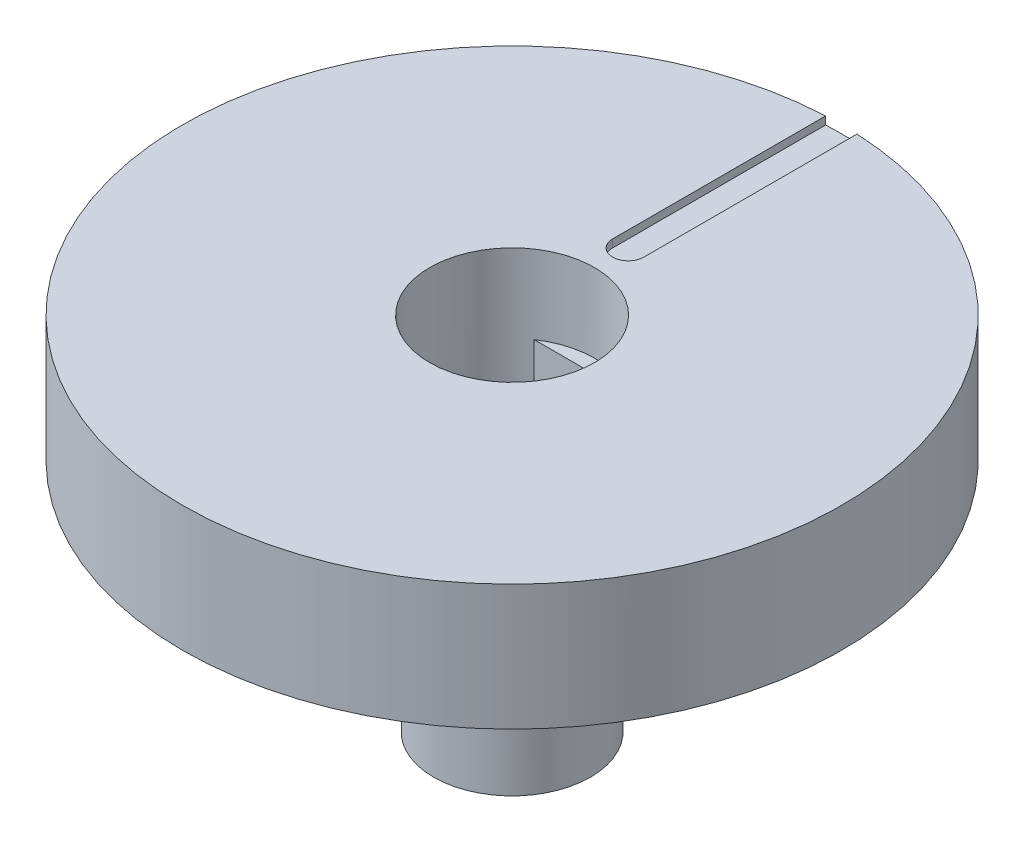
SolidWorks part; units mm, degrees
ref_plane "Front Plane" through (0, 0, 0) normal (0, 0, 1) x (1, 0, 0)
ref_plane "Top Plane" through (0, 0, 0) normal (0, 1, 0) x (1, 0, 0)
ref_plane "Right Plane" through (0, 0, 0) normal (1, 0, 0) x (0, 0, -1)
sketch "Sketch1" plane through (0, 0, 0) normal (0, 1, 0) x (1, 0, 0)
  circle A0 centre (0, 0) radius 8.6
  circle A1 centre (0, 0) radius 10.5
  dimension "D1" = 17.2
  dimension "D2" = 21
extrude "Boss-Extrude1" add sketch "Sketch1" against normal blind 3.5
ref_plane "Plane1" through (0, 0, 8.6) normal (0, 0, -1) x (-1, 0, 0)
sketch "Sketch2" plane through (0, 0, 8.6) normal (0, 0, -1) x (-1, 0, 0)
  line L0 (0.4, -2.9) -> (-0.4, -2.9)
  line L1 (0.4, -2.9) -> (0.4, -1)
  line L2 (0.4, -1) -> (1.4, 0)
  line L3 (10.5, 0) -> (-10.5, 0) construction
  line L4 (1.4, 0) -> (-1.4, 0)
  line L5 (-1.4, 0) -> (-0.4, -1)
  line L6 (-0.4, -1) -> (-0.4, -2.9)
  point P2 (0, -2.9)
  dimension "D1" = 2.9
  dimension "D2" = 135
  dimension "D3" = 135
  dimension "D4" = 0.8
  dimension "D5" = 1
extrude "Boss-Extrude2" add sketch "Sketch2" along normal blind 1.25
ref_plane "Plane2" through (0, 0, -8.6) normal (0, 0, 1) x (1, 0, 0)
extrude "Boss-Extrude3" add sketch "Sketch2<2>" against normal blind 1.25 from surface starting at plane "Plane2"
sketch "Sketch2<2>" plane through (0, 0, 8.6) normal (0, 0, -1) x (-1, 0, 0) same geometry as "Sketch2"
sketch "Sketch3" plane through (0, 0, 0) normal (0, 1, 0) x (1, 0, 0)
  circle A1 centre (0, 0) radius 10.5
  circle A2 centre (0, 0) radius 10.5
  dimension "D1" = 0
extrude "Boss-Extrude4" add sketch "Sketch3" along normal blind 0.5
sketch "Sketch5" plane through (0, 0, 0) normal (0, -1, 0) x (1, 0, 0)
  circle A1 centre (0, 0) radius 3.25
  dimension "D2" = 6.5
extrude "Boss-Extrude5" add sketch "Sketch5" along normal blind 6
fillet "Fillet2" radius 0.75 1 edges at (0, 0, 3.25)
sketch "Sketch4" plane through (0, 0.5, 0) normal (0, 1, 0) x (1, 0, 0)
  line L0 (-1.4697, 2.175) -> (1.4697, 2.175)
  line L1 (-3.1755, -2.625) -> (3.3726, -2.625) construction
  arc A0 (-1.4697, 2.175) -> (1.4697, 2.175) centre (0, 0) ccw
  dimension "D1" = 5.25
  dimension "D2" = 4.8
extrude "Cut-Extrude1" cut sketch "Sketch4" against normal blind 5.5
fillet "Fillet1" radius 0.25 4 edges at (-0.4, -2.9, 7.9703) (0.4, -2.9, 7.9703) (-0.4, -2.9, -7.9703) (0.4, -2.9, -7.9703)
sketch "Sketch7" plane through (0, 0.5, 0) normal (0, 1, 0) x (1, 0, 0)
  circle A2 centre (0, 0) radius 2.625
  arc A3 (-1.4697, 2.175) -> (1.4697, 2.175) centre (0, 0) ccw construction
extrude "Cut-Extrude2" cut sketch "Sketch7" against normal blind 2.5
sketch "Sketch9" plane through (0, 0.5, 0) normal (0, 1, 0) x (1, 0, 0)
  line L0 (0, 3.7) -> (0, 13.7) construction
  line L1 (-0.5, 3.7) -> (-0.5, 13.7)
  line L2 (0.5, 3.7) -> (0.5, 13.7)
  arc A0 (-0.5, 3.7) -> (0.5, 3.7) centre (0, 3.7) ccw
  arc A1 (0.5, 13.7) -> (-0.5, 13.7) centre (0, 13.7) ccw
  point P3 (0, 8.7)
  dimension "D1" = 1
  dimension "D2" = 10
  dimension "D3" = 3.7
extrude "Cut-Extrude3" cut sketch "Sketch9" against normal blind 0.25
sketch "Sketch11" plane through (0, -6, 0) normal (0, -1, 0) x (1, 0, 0)
  circle A0 centre (0, 0) radius 2.5
  dimension "D1" = 5
extrude "Boss-Extrude6" add sketch "Sketch11" along normal blind 5
sketch "Sketch10" plane through (0, -6, 0) normal (0, -1, 0) x (1, 0, 0)
  line L1 (1.8042, 0) -> (0.9021, 1.5625)
  line L2 (0.9021, 1.5625) -> (-0.9021, 1.5625)
  line L3 (-0.9021, 1.5625) -> (-1.8042, 0)
  line L4 (-1.8042, 0) -> (-0.9021, -1.5625)
  line L5 (-0.9021, -1.5625) -> (0.9021, -1.5625)
  line L6 (0.9021, -1.5625) -> (1.8042, 0)
  circle A0 centre (0, 0) radius 1.5625 construction
  dimension "D1" = 3.125
extrude "Cut-Extrude4" cut sketch "Sketch10" against normal blind 4.5 from surface starting at face at (0, -11, -2.5)
chamfer "Chamfer2" distance 0.25 angle 45 6 edges at (-1.3532, -11, 0.7813) (-1.3532, -11, -0.7813) (0, -11, -1.5625) (1.3532, -11, -0.7813) (1.3532, -11, 0.7813) (0, -11, 1.5625)
fillet "Fillet3" radius 5 1 edges at (0, -6, -2.5)
